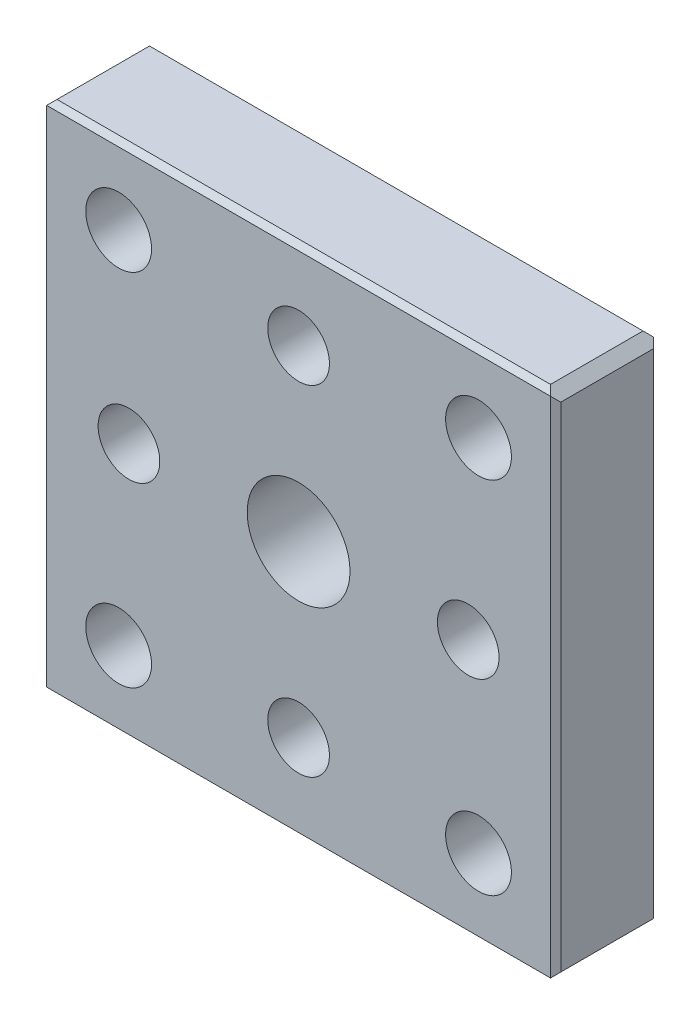
SolidWorks part; units mm, degrees
material "Plain Carbon Steel"
ref_plane "Front Plane" through (0, 0, 0) normal (0, 0, 1) x (1, 0, 0)
ref_plane "Top Plane" through (0, 0, 0) normal (0, 1, 0) x (1, 0, 0)
ref_plane "Right Plane" through (0, 0, 0) normal (1, 0, 0) x (0, 0, -1)
sketch "Sketch1" plane through (0, 0, 0) normal (0, 0, 1) x (1, 0, 0)
  line L1 (-25, -25) -> (25, -25)
  line L2 (-25, -25) -> (-25, 25)
  line L3 (-25, 25) -> (25, 25)
  line L4 (25, -25) -> (25, 25)
  line L5 (-25, -25) -> (25, 25) construction
  line L6 (-25, 25) -> (25, -25) construction
  point P0 (0, 0)
  dimension "D1" = 50
  dimension "D2" = 50
extrude "Boss-Extrude1" add sketch "Sketch1" along normal mid plane 10
hole_wizard "M6 Clearance Hole1" positions "Sketch4" profile "Sketch3" hole size "M6" standard "ISO" end condition through all
sketch "Sketch4" plane through (0, 0, 5) normal (0, 0, 1) x (1, 0, 0)
  line L0 (-25, 0) -> (25, 0) construction
  line L1 (-25, 25) -> (-25, -25) construction
  line L2 (25, -25) -> (25, 25) construction
  line L4 (0, 25) -> (0, -25) construction
  line L5 (25, 25) -> (-25, 25) construction
  line L6 (-25, -25) -> (25, -25) construction
  point P0 (-17.5, 17.5)
  point P2 (17.5, 17.5)
  point P4 (17.5, -17.5)
  point P6 (-17.5, -17.5)
  dimension "D1" = 35
  dimension "D2" = 35
sketch "Sketch3" plane through (-17.5, 17.5, 5) normal (1, 0, 0) x (0, -1, 0)
  line L0 (0, 0) -> (0, 10)
  line L1 (0, 10) -> (3.2, 10)
  line L2 (3.2, 10) -> (3.2, 0)
  line L5 (3.2, 0) -> (0, 0)
  line L11 (0, -6.35) -> (0, 107.95) construction
  dimension "Thru Hole Dia." = 6.4
  dimension "Thru Hole Depth" = 10
sketch "Sketch5" plane through (0, 0, 5) normal (0, 0, 1) x (1, 0, 0)
  circle A0 centre (0, 0) radius 5
  dimension "D1" = 10
extrude "Cut-Extrude1" cut sketch "Sketch5" against normal up to next
sketch "Sketch6" plane through (0, 0, -5) normal (0, 0, -1) x (-1, 0, 0)
  circle A0 centre (0, 0) radius 19
  dimension "D1" = 38
chamfer "Chamfer1" distance 1 angle 45 4 edges at (25, -25, 0) (-25, -25, 0) (-25, 25, 0) (25, 25, 0)
chamfer "Chamfer2" distance 0.5 angle 45 8 edges at (0, -25, 5) (0, -25, -5) (0, 25, -5) (0, 25, 5) (25, 0, -5) (25, 0, 5) (-25, 0, -5) (-25, 0, 5)
hole_wizard "Ø6.0 (6) Diameter Hole1" positions "Sketch9" profile "Sketch8" hole size "Ø6.0" standard "ISO" end condition through all
sketch "Sketch9" plane through (0, 0, -5) normal (0, 0, -1) x (-1, 0, 0)
  point P0 (-16.5, 0)
  point P3 (0, 16.5)
  point P6 (16.5, 0)
  point P9 (0, -16.5)
sketch "Sketch8" plane through (16.5, 0, -5) normal (1, 0, 0) x (0, 1, 0)
  line L0 (0, 0) -> (0, 10)
  line L1 (0, 10) -> (3, 10)
  line L2 (3, 10) -> (3, 0)
  line L5 (3, 0) -> (0, 0)
  line L11 (0, -6.35) -> (0, 107.95) construction
  dimension "Thru Hole Dia." = 6
  dimension "Thru Hole Depth" = 10
sketch "Sketch12" plane through (0, 0, -5) normal (0, 0, -1) x (-1, 0, 0)
  circle A1 centre (16.5, 0) radius 6.25 construction
  circle A3 centre (0, -16.5) radius 6.25 construction
  circle A5 centre (-16.5, 0) radius 6.25 construction
  circle A7 centre (0, 16.5) radius 6.25 construction
  circle A9 centre (16.5, 0) radius 6.25
  circle A11 centre (0, -16.5) radius 6.25
  circle A13 centre (-16.5, 0) radius 6.25
  circle A15 centre (0, 16.5) radius 6.25
extrude "Cut-Extrude2" cut sketch "Sketch12" against normal blind 3
sketch "Sketch13" plane through (0, 0, 5) normal (0, 0, 1) x (1, 0, 0)
  circle A0 centre (0, 0) radius 16.5 construction
